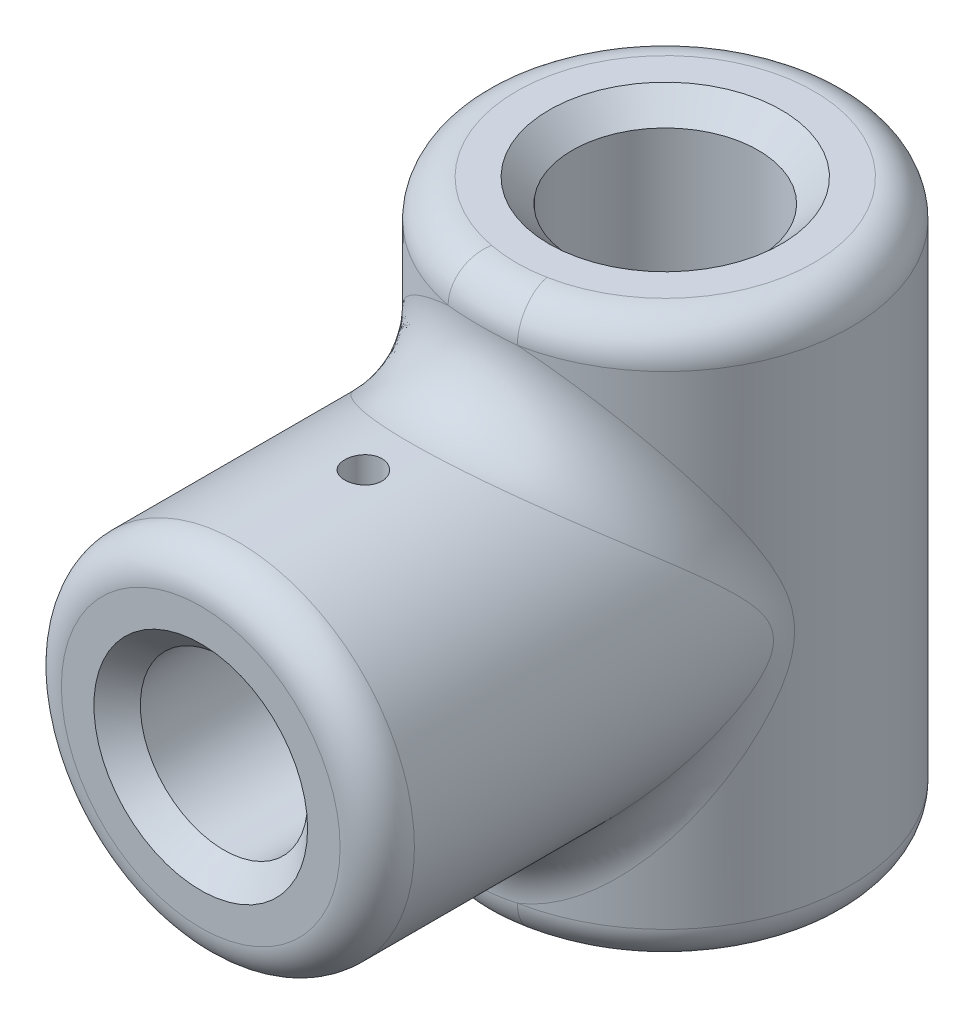
SolidWorks part; units mm, degrees
note: '?' marks a value the reader was unsure of.
ref_plane "Front Plane" through (0, 0, 0) normal (0, 0, 1) x (1, 0, 0)
ref_plane "Top Plane" through (0, 0, 0) normal (0, 1, 0) x (1, 0, 0)
ref_plane "Right Plane" through (0, 0, 0) normal (1, 0, 0) x (0, 0, -1)
sketch "Sketch1" plane through (0, 0, 0) normal (0, 1, 0) x (1, 0, 0)
  circle A0 centre (0, 0) radius 20
  circle A1 centre (0, 0) radius 40
  dimension "D1" = 40
  dimension "D2" = 20
extrude "Boss-Extrude1" add sketch "Sketch1" along normal mid plane 120
ref_plane "Plane1" through (0, 0, 40) normal (0, 0, 1) x (1, 0, 0)
sketch "Sketch2" plane through (0, 0, 40) normal (0, 0, 1) x (1, 0, 0)
  circle A0 centre (0, 0) radius 18
  circle A1 centre (0, 0) radius 38
  dimension "D2" = 36
  dimension "D1" = 20
extrude "Boss-Extrude2" add sketch "Sketch2" along normal blind 60 and the other way up to surface other way up to face at (0, 60, 40)
sketch "Sketch4" plane through (0, 0, 0) normal (0, 1, 0) x (1, 0, 0)
  line L0 (-19.8, -40) -> (19.8, -40) construction
  circle A0 centre (0, -65) radius 4
  dimension "D2" = 8
  dimension "D1" = 25
extrude "Cut-Extrude1" cut sketch "Sketch4" against normal through all both and the other way through all
fillet "Fillet2" radius 15 1 edges at (37.9463, 2.0194, 12.6522)
chamfer "Chamfer1" distance 5 angle 45 3 edges at (0, -60, 20) (0, 60, 20) (18, 0, 100)
fillet "Fillet3" radius 8 3 edges at (38, 0, 100) (0, -60, 40) (0, 60, 40)
ref_axis "Axis1" through (0, 0, 95) along (0, 0, -1)?
